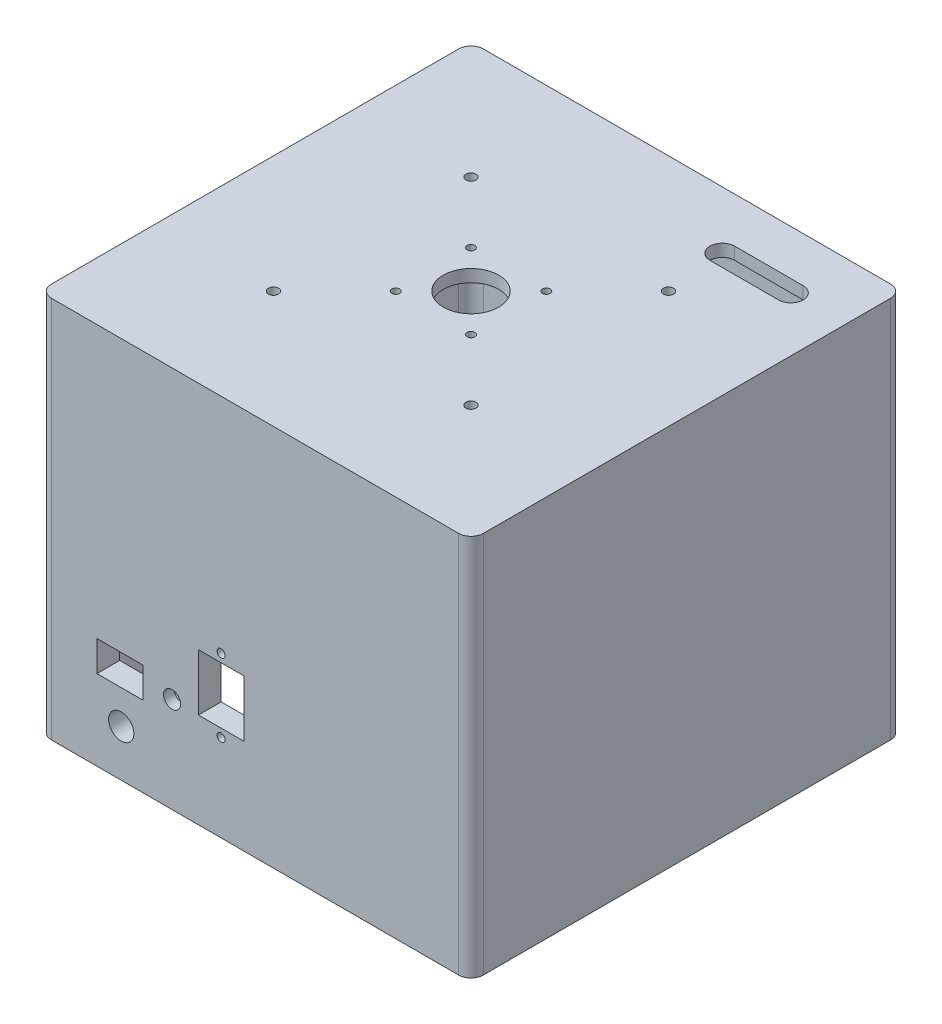
SolidWorks part; units mm, degrees
ref_plane "Front Plane" through (0, 0, 0) normal (0, 0, 1) x (1, 0, 0)
ref_plane "Top Plane" through (0, 0, 0) normal (0, 1, 0) x (1, 0, 0)
ref_plane "Right Plane" through (0, 0, 0) normal (1, 0, 0) x (0, 0, -1)
sketch "Sketch1" plane through (0, 0, 0) normal (0, 1, 0) x (1, 0, 0)
  line L1 (-83.82, -88.9) -> (83.82, -88.9)
  line L2 (-88.9, -83.82) -> (-88.9, 83.82)
  line L3 (-83.82, 88.9) -> (83.82, 88.9)
  line L4 (88.9, -83.82) -> (88.9, 83.82)
  line L5 (-88.9, -88.9) -> (88.9, 88.9) construction
  line L6 (-88.9, 88.9) -> (88.9, -88.9) construction
  line L11 (-64.7359, -64.7359) -> (-18.5761, -18.5761) construction
  line L12 (-23.0799, 23.0799) -> (23.0799, -23.0799) construction
  line L13 (-79.5394, -79.5394) -> (79.5394, -79.5394)
  line L14 (-79.5394, -79.5394) -> (-79.5394, 79.5394)
  line L15 (-79.5394, 79.5394) -> (79.5394, 79.5394)
  line L16 (79.5394, -79.5394) -> (79.5394, 79.5394)
  line L17 (-79.5394, -79.5394) -> (79.5394, 79.5394) construction
  line L18 (-79.5394, 79.5394) -> (79.5394, -79.5394) construction
  circle A0 centre (0, 0) radius 11.43
  arc A1 (-83.82, -88.9) -> (-88.9, -83.82) centre (-83.82, -83.82) cw
  arc A2 (83.82, -88.9) -> (88.9, -83.82) centre (83.82, -83.82) ccw
  arc A3 (83.82, 88.9) -> (88.9, 83.82) centre (83.82, 83.82) cw
  arc A4 (-88.9, 83.82) -> (-83.82, 88.9) centre (-83.82, 83.82) cw
  point P0 (0, 0)
  point P6 (0, 0)
  point P11 (0, 0)
  dimension "D3" = 22.86
  dimension "D2" = 5.08
  dimension "D1" = 177.8
extrude "Boss-Extrude1" add sketch "Sketch1" along normal blind 101.6 and the other way blind 50.8 contours L1 L4 L3 L2 L16 L13 L14 L15 region at (-85.6341, 0, 85.6341)
extrude "Boss-Extrude3" add sketch "Sketch1<5>" along normal blind 5.08 from surface contours L1 L4 L3 L2 L16 L13 L14 L15 | L13 L16 L15 L14 region at (-85.6341, 0, 85.6341) region at (-77.2897, 0, 0) starting at face at (0, 101.6, 0)
sketch "Sketch1<5>" plane through (0, 0, 0) normal (0, 1, 0) x (1, 0, 0) same geometry as "Sketch1"
sketch "Sketch3" plane through (0, 106.68, 0) normal (0, 1, 0) x (1, 0, 0)
  line L0 (0, 88.9) -> (0, -88.9) construction
  line L2 (-88.9, 0) -> (88.9, 0) construction
  line L3 (88.9, 83.82) -> (88.9, -83.82) construction
  line L4 (83.82, -88.9) -> (-83.82, -88.9) construction
  circle A0 centre (-15.5, 15.5) radius 1.6
  circle A1 centre (-15.5, -15.5) radius 1.6
  circle A2 centre (15.5, 15.5) radius 1.6
  circle A3 centre (15.5, -15.5) radius 1.6
  point P7 (0, 0)
  point P14 (0, 0)
  point P15 (0, 0)
  dimension "D1" = 3.2
  dimension "D2" = 15.5
  dimension "D3" = 15.5
extrude "Cut-Extrude1" cut sketch "Sketch3" against normal through all
fillet "Fillet4" radius 5.08 4 edges at (-79.5394, 25.4, -79.5394) (-79.5394, 25.4, 79.5394) (79.5394, 25.4, 79.5394) (79.5394, 25.4, -79.5394)
sketch "Sketch4" plane through (0, 106.68, 0) normal (0, 1, 0) x (1, 0, 0)
  line L0 (0, 88.9) -> (0, -88.9) construction
  line L1 (83.82, -88.9) -> (-83.82, -88.9) construction
  line L2 (-88.9, 0) -> (88.9, 0) construction
  line L3 (88.9, 83.82) -> (88.9, -83.82) construction
  circle A0 centre (-40.66, 40.66) radius 2.1
  circle A1 centre (40.66, 40.66) radius 2.1
  circle A2 centre (-40.66, -40.66) radius 2.1
  circle A3 centre (40.66, -40.66) radius 2.1
  point P7 (0, 0)
  point P14 (0, 0)
  dimension "D1" = 4.2
  dimension "D2" = 40.66
  dimension "D3" = 40.66
extrude "Cut-Extrude2" cut sketch "Sketch4" against normal up to surface (5.08 mm away) up to face at (15.5, 101.6, 17.1)
sketch "Sketch5" plane through (0, 0, 88.9) normal (0, 0, 1) x (1, 0, 0)
  line L0 (-13.97, 15.0114) -> (-13.97, -15.0114) construction
  line L1 (-65.0849, -5.2683) -> (-46.0849, -5.2683)
  line L2 (-65.0849, -5.2683) -> (-65.0849, -17.7683)
  line L3 (-65.0849, -17.7683) -> (-46.0849, -17.7683)
  line L4 (-46.0849, -5.2683) -> (-46.0849, -17.7683)
  line L5 (-23.32, 11.65) -> (-4.62, 11.65)
  line L6 (-23.32, 11.65) -> (-23.32, -11.65)
  line L7 (-23.32, -11.65) -> (-4.62, -11.65)
  line L8 (-4.62, 11.65) -> (-4.62, -11.65)
  line L9 (-23.32, 11.65) -> (-4.62, -11.65) construction
  line L10 (-23.32, -11.65) -> (-4.62, 11.65) construction
  line L11 (-83.82, -50.8) -> (-83.82, 106.68) construction
  line L12 (-83.82, -50.8) -> (83.82, -50.8) construction
  circle A0 centre (-34.1586, -11.5183) radius 3.5
  circle A2 centre (-55.1023, -31.6253) radius 5.207
  circle A3 centre (-13.97, 15.0114) radius 1.65
  circle A4 centre (-13.97, -15.0114) radius 1.65
  point P7 (-46.0849, -11.5183)
  point P14 (-13.97, 0)
  dimension "D3" = 7
  dimension "D4" = 10.414
  dimension "D5" = 3.3
  dimension "D6" = 3.3
  dimension "D13" = 28.7177
  dimension "D1" = 19
  dimension "D2" = 12.5
  dimension "D7" = 30.0228
  dimension "D8" = 23.3
  dimension "D9" = 18.7
  dimension "D10" = 69.85
  dimension "D11" = 50.8
  dimension "D12" = 18.7351
  dimension "D14" = 11.9263
extrude "Cut-Extrude3" cut sketch "Sketch5" against normal up to surface (9.3606 mm away) up to face at (0, 25.4, 79.5394)
sketch "Sketch7" plane through (0, -50.8, 0) normal (0, -1, 0) x (1, 0, 0)
  line L0 (-74.4594, -79.5394) -> (74.4594, -79.5394) construction
  line L1 (-12.7, -84.6194) -> (12.7, -84.6194)
  line L2 (-12.7, -84.6194) -> (-12.7, -79.5394)
  line L3 (-12.7, -79.5394) -> (12.7, -79.5394)
  line L4 (12.7, -84.6194) -> (12.7, -79.5394)
  line L5 (-12.7, -84.6194) -> (12.7, -79.5394) construction
  line L6 (-12.7, -79.5394) -> (12.7, -84.6194) construction
  point P0 (0, -82.0794)
  dimension "D1" = 5.08
  dimension "D2" = 25.4
extrude "Cut-Extrude4" cut sketch "Sketch7" against normal blind 5.588
sketch "Sketch10" plane through (12.7, 0, 0) normal (-1, 0, 0) x (0, 0, 1)
  line L0 (-79.5394, -38.354) -> (-79.5394, -41.148)
  line L1 (-81.0634, -41.148) -> (-79.5394, -41.148)
  line L3 (-79.5394, -50.8) -> (-79.5394, 101.6) construction
  line L4 (-81.0634, -41.148) -> (-79.5394, -38.354)
  dimension "D1" = 0
  dimension "D2" = 9.652
  dimension "D3" = 2.794
  dimension "D4" = 1.524
extrude "Boss-Extrude4" add sketch "Sketch10" along normal up to surface (25.4 mm away) up to face at (-12.7, -48.006, -82.0794)
extrude "Cut-Extrude5" cut sketch "Sketch10<2>" along normal up to surface (25.4 mm away) up to face at (-12.7, -48.006, -82.0794)
sketch "Sketch10<2>" plane through (12.7, 0, 0) normal (-1, 0, 0) x (0, 0, 1) same geometry as "Sketch10"
sketch "Sketch11" plane through (0, 0, 79.5394) normal (0, 0, -1) x (-1, 0, 0)
  line L1 (-50.8, -45.72) -> (-38.1, -45.72)
  line L2 (-50.8, -45.72) -> (-50.8, -41.148)
  line L3 (-50.8, -41.148) -> (-38.1, -41.148)
  line L4 (-38.1, -45.72) -> (-38.1, -41.148)
  line L5 (83.82, -50.8) -> (-83.82, -50.8) construction
  line L6 (0, -50.8) -> (0, -21.4618) construction
  line L7 (38.1, -45.72) -> (38.1, -41.148)
  line L8 (50.8, -41.148) -> (38.1, -41.148)
  line L9 (50.8, -45.72) -> (50.8, -41.148)
  line L10 (50.8, -45.72) -> (38.1, -45.72)
  dimension "D1" = 12.7
  dimension "D2" = 4.572
  dimension "D3" = 5.08
  dimension "D4" = 38.1
extrude "Cut-Extrude6" cut sketch "Sketch11" against normal blind 5.334
sketch "Sketch12" plane through (0, 106.68, 0) normal (0, 1, 0) x (1, 0, 0)
  line L0 (88.9, 83.82) -> (88.9, -83.82) construction
  line L1 (83.82, 88.9) -> (-83.82, 88.9) construction
  line L3 (38.2103, 70.3262) -> (66.436, 70.3262)
  line L5 (38.2103, 60.1662) -> (66.436, 60.1662)
  arc A1 (66.436, 60.1662) -> (66.436, 70.3262) centre (66.436, 65.2462) ccw
  arc A2 (38.2103, 70.3262) -> (38.2103, 60.1662) centre (38.2103, 65.2462) ccw
  point P0 (45.1923, 65.2462)
  dimension "D3" = 18.5738
  dimension "D2" = 22.464
  dimension "D6" = 5.08
  dimension "D1" = 10.16
  dimension "D4" = 28.2257
  dimension "D5" = 28.2257
extrude "Cut-Extrude7" cut sketch "Sketch12" against normal blind 2.54
extrude "Cut-Extrude8" cut sketch "Sketch12<2>" against normal blind 16.764
sketch "Sketch12<2>" plane through (0, 106.68, 0) normal (0, 1, 0) x (1, 0, 0) same geometry as "Sketch12"
sketch "Sketch13" plane through (0, 0, 79.5394) normal (0, 0, -1) x (-1, 0, 0)
  circle A0 centre (34.1586, -11.5183) radius 6.5
extrude "Cut-Extrude9" cut sketch "Sketch13" against normal blind 5.08
